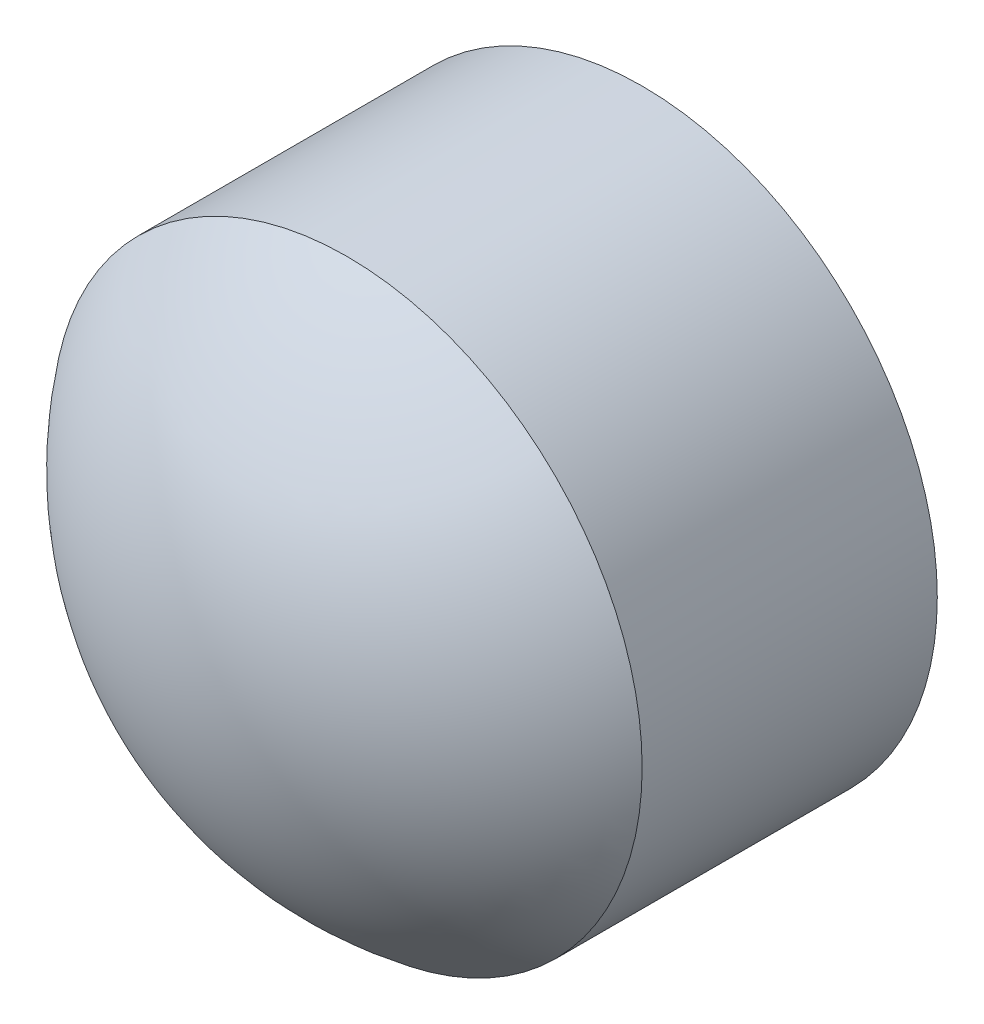
SolidWorks part; units mm, degrees
ref_plane "Front Plane" through (0, 0, 0) normal (0, 0, 1) x (1, 0, 0)
ref_plane "Top Plane" through (0, 0, 0) normal (0, 1, 0) x (1, 0, 0)
ref_plane "Right Plane" through (0, 0, 0) normal (1, 0, 0) x (0, 0, -1)
sketch "Sketch1" plane through (0, 0, 0) normal (0, 0, 1) x (1, 0, 0)
  circle A0 centre (0, 2.875) radius 1
  dimension "D1" = 2
extrude "Extrude1" add sketch "Sketch1" along normal blind 1
dome "Dome1" faces to dome 1 distance 0.5 reverse direction no elliptical dome no face at (1, 2.875, 1) parameters "D1"=0.5
